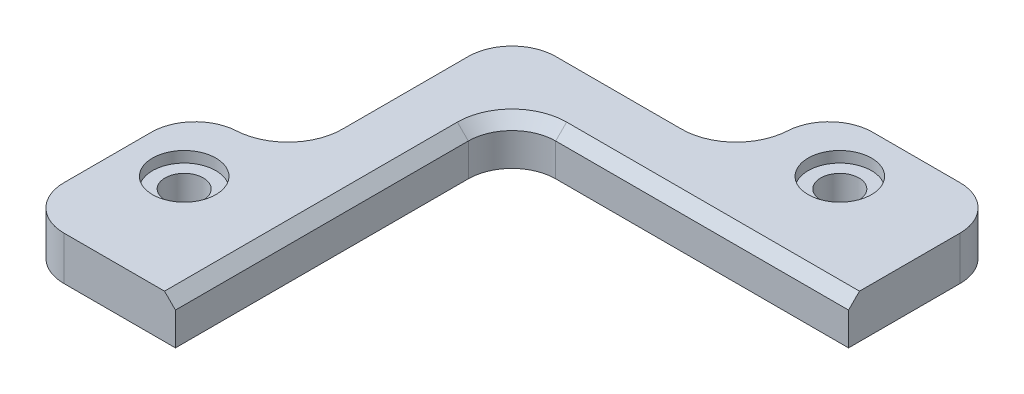
SolidWorks part; units mm, degrees
ref_plane "Alzado" through (0, 0, 0) normal (0, 0, 1) x (1, 0, 0)
ref_plane "Planta" through (0, 0, 0) normal (0, 1, 0) x (1, 0, 0)
ref_plane "Vista lateral" through (0, 0, 0) normal (1, 0, 0) x (0, 0, -1)
sketch "Croquis1" plane through (0, 0, 0) normal (0, 1, 0) x (1, 0, 0)
  line L0 (0, 0) -> (0, 45)
  line L1 (0, 45) -> (45, 45)
  line L2 (45, 45) -> (45, 35)
  line L3 (45, 35) -> (10, 35)
  line L4 (10, 35) -> (10, 0)
  line L5 (10, 0) -> (0, 0)
  line L6 (5, 0) -> (5, 45) construction
  line L7 (45, 40) -> (0, 40) construction
  circle A0 centre (35, 40) radius 1.75
  circle A1 centre (5, 10) radius 1.75
  dimension "D3" = 3.5
  dimension "D4" = 3.5
  dimension "D1" = 10
  dimension "D2" = 10
  dimension "D5" = 30
  dimension "D6" = 30
  dimension "D7" = 45
  dimension "D8" = 45
extrude "Saliente-Extruir1" add sketch "Croquis1" along normal blind 4
sketch "Croquis2" plane through (0, 4, 0) normal (0, 1, 0) x (1, 0, 0)
  line L0 (10, 35) -> (45, 35) construction
  line L1 (10, 0) -> (14.2, 0)
  line L2 (10, 0) -> (10, 35)
  line L3 (10, 35) -> (14.2, 35)
  line L4 (14.2, 0) -> (14.2, 35)
  line L6 (45, 35) -> (14.2, 35)
  line L7 (45, 35) -> (45, 30.8)
  line L8 (45, 30.8) -> (14.2, 30.8)
  line L9 (14.2, 35) -> (14.2, 30.8)
  line M6 (10, 0) -> (10, 35)
  line M7 (10, 35) -> (45, 35)
  dimension "D1" = 4.2
  dimension "D2" = 4.2
extrude "Saliente-Extruir2" add sketch "Croquis2" against normal up to surface (4 mm away) contours L8 L7 L4 M7 | L1 L4 M7 M6 region at (12.1, 4, -17.5) region at (29.6, 4, -32.9) up to face at (35, 0, -38.25)
sketch "Croquis3" plane through (0, 4, 0) normal (0, 1, 0) x (1, 0, 0)
  line L1 (0, 45) -> (29, 45)
  line L2 (0, 45) -> (0, 36.5)
  line L3 (0, 36.5) -> (29, 36.5)
  line L4 (29, 45) -> (29, 36.5)
  line L5 (0, 36.5) -> (8.5, 36.5)
  line L6 (0, 36.5) -> (0, 16)
  line L7 (0, 16) -> (8.5, 16)
  line L8 (8.5, 36.5) -> (8.5, 16)
  line M9 (45, 45) -> (0, 45)
  line M10 (0, 45) -> (0, 0)
  dimension "D1" = 8.5
  dimension "D2" = 29
  dimension "D3" = 8.5
  dimension "D4" = 20.5
extrude "Cortar-Extruir1" cut sketch "Croquis3" against normal up to surface (4 mm away) contours L4 L3 M9 M10 | L8 L3 L7 M10 region at (14.5, 4, -40.75) region at (4.25, 4, -26.25) up to face at (35, 0, -38.25)
fillet "Redondeo1" radius 4 2 edges at (14.2, 2, -30.8) (8.5, 2, -36.5)
fillet "Redondeo2" radius 4 4 edges at (0, 2, 0) (0, 2, -16) (29, 2, -45) (45, 2, -45)
chamfer "Chaflán1" distance 1 angle 45 3 edges at (14.2, 4, -13.4) (15.3716, 4, -29.6284) (31.6, 4, -30.8)
sketch "Croquis4" plane through (0, 4, 0) normal (0, 1, 0) x (1, 0, 0)
  circle A0 centre (35, 40) radius 2.9
  circle A1 centre (5, 10) radius 2.9
  dimension "D1" = 5.8
  dimension "D2" = 5.8
extrude "Cortar-Extruir2" cut sketch "Croquis4" against normal blind 1
fillet "Redondeo3" radius 5 2 edges at (8.5, 2, -16) (29, 2, -36.5)
